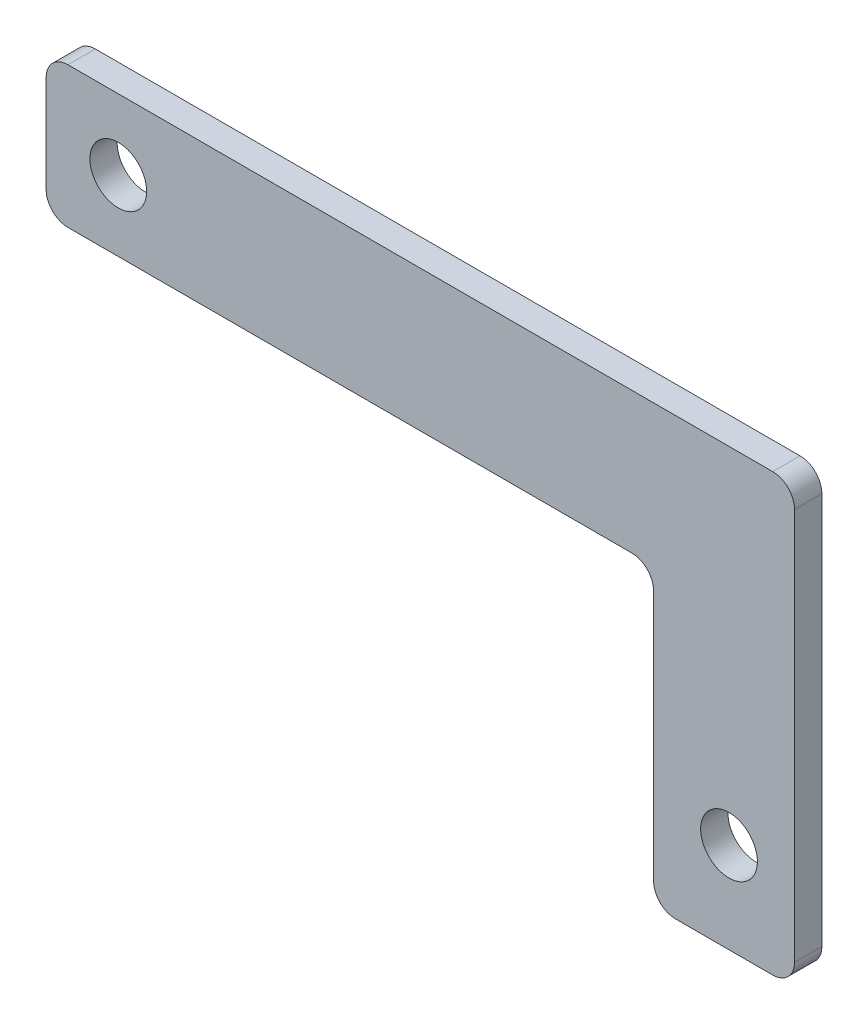
SolidWorks part; units mm, degrees
material "Copper"
ref_plane "X-Y Datum" through (0, 0, 0) normal (0, 0, 1) x (1, 0, 0)
ref_plane "X-Z Datum" through (0, 0, 0) normal (0, 1, 0) x (1, 0, 0)
ref_plane "Y-Z Datum" through (0, 0, 0) normal (1, 0, 0) x (0, 0, -1)
sketch "Sketch1" plane through (0, 0, 0) normal (0, 0, 1) x (1, 0, 0)
  line L0 (55.9906, -112.7916) -> (55.9906, -87.1585) construction
  line L15 (-22.7939, -70.3126) -> (38.0997, -70.3126) construction
  line L20 (47.8016, -78.5016) -> (-22.7939, -78.5016)
  line L22 (64.1796, -62.1236) -> (-22.7939, -62.1236)
  line L23 (-22.7939, -78.5016) -> (-22.7939, -62.1236)
  line L25 (64.1796, -62.1236) -> (64.1796, -112.7916)
  line L26 (64.1796, -112.7916) -> (47.8016, -112.7916)
  line L27 (47.8016, -78.5016) -> (47.8016, -112.7916)
  line L28 (64.9733, -75.7002) -> (64.9733, -113.8002) construction
  circle A0 centre (10, -8.189) radius 4 construction
  point P4 (-14.4119, -70.3126)
  point P9 (94.5499, -37.3736)
  point P10 (56.5659, -102.2686)
  point P26 (94.5499, -37.3736)
  dimension "D3" = 8
  dimension "D1" = 0.7937
  dimension "D2" = 34.29
  dimension "D4" = 16.378
  dimension "D5" = 8.382
  dimension "D6" = 16.378
base flange "Base-Flange1" sketch "Sketch1" thickness 3.175 reverse thickness direction no parameters "D1"=0.7366
hole_wizard "M6 Clearance Hole1" positions "Sketch19" profile "Sketch20" hole size "M6" standard "ANSI Metric" end condition through all
sketch "Sketch19" plane through (0, 0, 0) normal (0, 0, 1) x (1, 0, 0)
  point P3 (56.5659, -102.2686)
  point P9 (-14.4119, -70.3126)
sketch "Sketch20" plane through (56.5659, -102.2686, 0) normal (1, 0, 0) x (0, -1, 0)
  line L0 (0, 0) -> (0, 3.175)
  line L1 (0, 3.175) -> (3.3, 3.175)
  line L2 (3.3, 3.175) -> (3.3, 0)
  line L5 (3.3, 0) -> (0, 0)
  line L11 (0, -6.35) -> (0, 107.95) construction
  dimension "Thru Hole Dia." = 6.6
  dimension "Thru Hole Depth" = 3.175
fillet "Fillet1" radius 2.54 6 edges at (64.1796, -112.7916, -1.5875) (47.8016, -112.7916, -1.5875) (47.8016, -78.5016, -1.5875) (64.1796, -62.1236, -1.5875) (-22.7939, -62.1236, -1.5875) (-22.7939, -78.5016, -1.5875)
sketch "Bend-Lines1" [suppressed] plane through (0, 0, 0) normal (0, 1, 0) x (1, 0, 0)
sketch "Bounding-Box1" [suppressed] plane through (0, 0, 0) normal (0, 1, 0) x (1, 0, 0)
sheet metal parameters "Sheet-Metal3" thickness 3.175 parameters "D1"=0.7366
flat pattern "Flat-Pattern3" [suppressed]
sketch "Bend-Lines2" plane through (0, 0, 0) normal (0, 1, 0) x (1, 0, 0)
sketch3d "Bounding-Box2" [suppressed]
  line L0 (0, -16.378, 0) -> (-76.2, -16.378, 0) construction
  line L1 (0, 0, 0) -> (-76.2, 0, 0) construction
  line L2 (0, -16.378, 0) -> (0, 0, 0) construction
  line L3 (-76.2, -16.378, 0) -> (-76.2, 0, 0) construction
sheet metal parameters "Sheet-Metal8" thickness 3.175 parameters "D1"=0.7366
flat pattern "Flat-Pattern3"
sketch "Bend-Lines2" plane through (0, 0, 0) normal (0, 0, 1) x (1, 0, 0)
sketch3d "Bounding-Box2" [suppressed]
  line L0 (-22.7939, -112.7916, 0) -> (64.1796, -112.7916, 0) construction
  line L1 (-22.7939, -62.1236, 0) -> (64.1796, -62.1236, 0) construction
  line L2 (-22.7939, -112.7916, 0) -> (-22.7939, -62.1236, 0) construction
  line L3 (64.1796, -112.7916, 0) -> (64.1796, -62.1236, 0) construction
